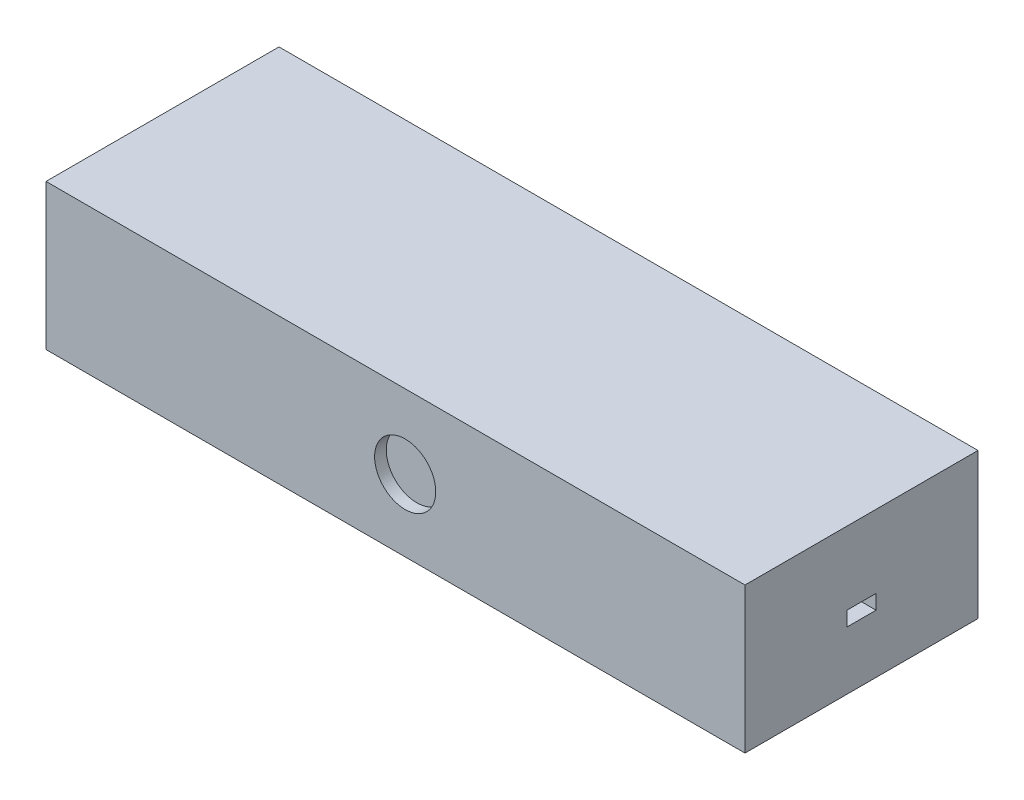
SolidWorks part; units mm, degrees
ref_plane "Front Plane" through (0, 0, 0) normal (0, 0, 1) x (1, 0, 0)
ref_plane "Top Plane" through (0, 0, 0) normal (0, 1, 0) x (1, 0, 0)
ref_plane "Right Plane" through (0, 0, 0) normal (1, 0, 0) x (0, 0, -1)
sketch "Sketch1" plane through (0, 0, 0) normal (0, 1, 0) x (1, 0, 0)
  line L0 (0, 0) -> (0, 80)
  line L1 (0, 80) -> (240, 80)
  line L2 (240, 80) -> (240, 0)
  line L3 (240, 0) -> (0, 0)
  dimension "D1" = 80
  dimension "D2" = 240
extrude "Boss-Extrude1" add sketch "Sketch1" along normal blind 50
sketch "Sketch2" plane through (0, 0, 0) normal (0, 1, 0) x (1, 0, 0)
  line L0 (120, 80) -> (180, 80) construction
  line L1 (240, 80) -> (0, 80) construction
  line L2 (180, 80) -> (180, 0) construction
  line L3 (240, 40) -> (149.3517, 40) construction
  line L5 (202.5, 50.5) -> (202.5, 29.5)
  line L6 (202.5, 50.5) -> (157.5, 50.5)
  line L7 (157.5, 50.5) -> (157.5, 29.5)
  line L8 (202.5, 29.5) -> (157.5, 29.5)
  point P13 (180, 50.5)
  point P14 (202.5, 40)
  point P15 (157.5, 40)
  dimension "D1" = 60
  dimension "D2" = 21
  dimension "D3" = 22.5
extrude "Cut-Extrude1" cut sketch "Sketch2" along normal blind 28
sketch "Sketch3" plane through (0, 0, 0) normal (0, 0, 1) x (1, 0, 0)
  line L0 (37.9188, 24.5841) -> (-38.0812, 24.5841) construction
  line L1 (123.3203, 30.4936) -> (123.3203, -29.5064) construction
  circle A0 centre (123.3203, 24.5841) radius 10.5
  dimension "D1" = 21
extrude "Cut-Extrude2" cut sketch "Sketch3" against normal blind 4
sketch "Sketch4" plane through (0, 0, 0) normal (1, 0, 0) x (0, 0, -1)
  line L0 (40, 0) -> (40, 20) construction
  line L1 (0, 0) -> (80, 0) construction
  line L2 (40, 20) -> (45, 20) construction
  line L3 (45, 20) -> (35, 20)
  line L4 (35, 20) -> (35, 25)
  line L5 (35, 25) -> (45, 25)
  line L6 (45, 25) -> (45, 20)
  dimension "D1" = 20
  dimension "D2" = 5
  dimension "D3" = 10
  dimension "D4" = 5
extrude "Cut-Extrude3" cut sketch "Sketch4" against normal blind 40 from offset 240
